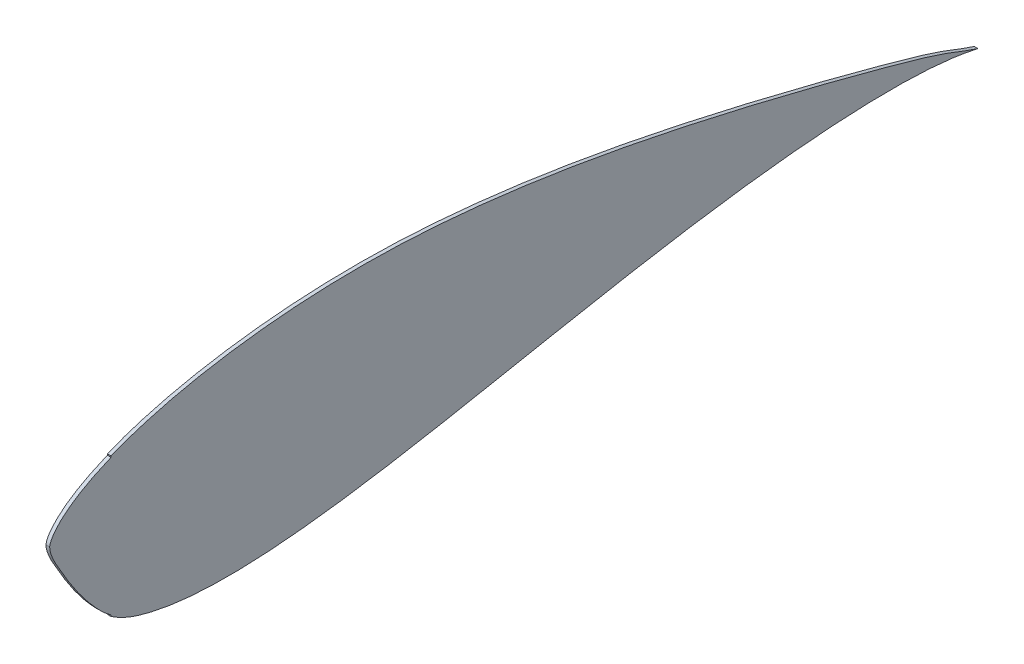
SolidWorks part; units mm, degrees
material "Custom Carbon Fiber"
ref_plane "Front Plane" through (0, 0, 0) normal (0, 0, 1) x (1, 0, 0)
ref_plane "Top Plane" through (0, 0, 0) normal (0, 1, 0) x (1, 0, 0)
ref_plane "Right Plane" through (0, 0, 0) normal (1, 0, 0) x (0, 0, -1)
ref_plane "Plane1" through (266.7, 0, 0) normal (1, 0, 0) x (0, 0, -1)
sketch "Sketch2" plane through (266.7, 0, 0) normal (1, 0, 0) x (0, 0, -1)
  line L0 (53.975, 13.9347) -> (53.975, 40.3347) construction
  line L1 (53.975, -78.4194) -> (53.975, 41.651)
  spline S0 degree 1 poles (789.2908, -24.5075) (1.0009, -0.0106) knots 0 0 1 1 construction
  spline S1 degree 1 poles (1.0009, -0.0106) (789.2908, -24.5075) knots 0 0 1 1 construction
  spline S2 degree 3 poles (789.2908, -24.5075) (785.3163, -22.9509) (777.3554, -19.854) (761.2394, -14.2813) (740.7218, -8.356) (715.9964, -1.5357) (691.2078, 5.039) (666.3726, 11.4509) (633.2067, 19.788) (591.6453, 29.7876) (541.5821, 40.9551) (491.2968, 51.0591) (440.7669, 59.8425) (389.9856, 66.9978) (347.468, 71.3203) (313.3654, 73.5459) (279.214, 74.78) (245.0298, 74.5204) (210.9104, 72.6538) (185.3864, 70.3744) (159.9555, 67.2138) (134.6626, 63.1156) (109.5715, 57.9457) (88.911, 52.5848) (72.6183, 47.5158) (60.5547, 43.2587) (48.7006, 38.47) (37.1259, 33.0527) (27.8301, 27.8819) (20.7191, 23.2421) (15.6145, 19.4551) (10.7867, 15.3221) (6.4295, 10.7521) (3.3298, 6.5207) (1.7664, 3.2894) (1.2346, 1.6296) (1.0709, 0.8085) (1.0227, 0.3736) (1.0078, 0.114) (1.0009, -0.0106) knots 0.015898 0.015898 0.015898 0.015898 0.031274 0.04665 0.077401 0.108153 0.138904 0.169656 0.200407 0.26191 0.323413 0.384916 0.446419 0.507923 0.569426 0.600177 0.630929 0.692432 0.723183 0.753935 0.784686 0.815438 0.846189 0.876941 0.892316 0.907692 0.923068 0.938444 0.95382 0.961507 0.969195 0.976883 0.984571 0.992259 0.996103 0.998025 0.998986 0.999466 0.999947 0.999947 0.999947 0.999947
  spline S3 degree 3 poles (1.0009, -0.0106) (1.0099, -0.2779) (1.0289, -0.8234) (1.1028, -1.8259) (1.4168, -3.5972) (2.4522, -7.2032) (4.5577, -12.1314) (7.6943, -17.8738) (12.0815, -25.4664) (17.7322, -34.7965) (24.9199, -45.7682) (31.4576, -54.481) (37.0476, -61.1825) (42.8536, -67.72) (50.6545, -75.2474) (61.6337, -82.3376) (73.6522, -87.3558) (86.2831, -90.8757) (99.0883, -93.5961) (116.3556, -96.1813) (138.1724, -97.7923) (164.4147, -97.9546) (190.6442, -96.7472) (216.8104, -94.5068) (242.9011, -91.4628) (277.5889, -86.5748) (320.7803, -79.293) (372.4416, -69.5597) (424.0475, -59.4829) (475.6974, -49.5822) (527.4768, -40.324) (579.4491, -32.1431) (631.6563, -25.5197) (675.3681, -21.7598) (710.4397, -20.2592) (736.775, -20.0353) (763.1229, -21.0632) (780.614, -23.101) (789.2908, -24.5075) knots 0.000052 0.000052 0.000052 0.000052 0.001013 0.001974 0.003897 0.007743 0.015433 0.023124 0.030815 0.046197 0.061579 0.07696 0.084651 0.092342 0.107724 0.123105 0.138487 0.153869 0.16925 0.184632 0.215396 0.246159 0.276922 0.307686 0.338449 0.369213 0.430739 0.492266 0.553793 0.61532 0.676847 0.738374 0.7999 0.861427 0.892191 0.922954 0.953717 0.984481 0.984481 0.984481 0.984481
  spline S4 degree 3 poles (-998.6585, -47.5543) (30.9847, 34.8549) (-3.0916, 14.059) (0.5702, -4.3968) (2.5361, -10.6164) (7.9982, -20.5501) (16.1137, -34.185) (25.7513, -48.9002) (36.932, -62.9388) (49.3364, -75.9186) (65.2269, -85.625) (84.4528, -91.7174) (106.8521, -96.1515) (132.5109, -98.5722) (161.1944, -99.0924) (192.7613, -97.7042) (227.0382, -94.5118) (263.8348, -89.6638) (302.9215, -83.3884) (344.0178, -75.9778) (386.7768, -67.7807) (430.7746, -59.2023) (475.4963, -50.6638) (520.3353, -42.6036) (564.5889, -35.4228) (607.4709, -29.4733) (648.1275, -25.0145) (685.6676, -22.1862) (719.1968, -21.0048) (747.8303, -21.2786) (770.6884, -22.8547) (787.0914, -25.0735) (843.5368, -35.1796) (888.9653, -70.6457) (1145.7828, 910.9381) knots -0.056641 -0.056641 -0.056641 -0.056641 0.001821 0.004613 0.009135 0.024676 0.044153 0.064937 0.086321 0.107138 0.1276 0.150893 0.177565 0.207668 0.241222 0.278203 0.318526 0.362031 0.408465 0.457479 0.508614 0.561296 0.614835 0.668438 0.721214 0.772202 0.820393 0.864766 0.904324 0.938132 0.965242 0.98469 0.99621 1.166448 1.166448 1.166448 1.166448 only from (0, 0) to (802.1511, -28.0117) construction
  spline S5 degree 3 poles (592.9551, -1005.8033) (880.8278, -21.537) (831.6126, -40.0251) (789.3572, -23.4586) (777.0615, -18.6436) (760.5817, -13.0401) (739.9968, -7.1233) (715.5772, -0.3798) (687.647, 7.013) (656.6835, 14.9584) (623.1589, 23.2583) (587.5492, 31.6944) (550.3192, 40.0262) (511.9148, 48.0016) (472.7617, 55.3745) (433.2622, 61.9128) (393.7959, 67.4048) (354.7199, 71.6552) (316.357, 74.5357) (278.9313, 75.7536) (242.6994, 75.3938) (207.8706, 73.5467) (174.7468, 70.259) (143.6014, 65.7682) (114.7621, 60.1875) (88.5345, 53.6285) (65.199, 46.2382) (45.0006, 38.1339) (28.1586, 29.5092) (14.871, 20.5578) (6.1442, 12.3133) (1.9481, 6.1765) (0.6391, 3.0841) (0.217, 1.668) (-1.7676, -8.4574) (19.8775, -20.5223) (-997.5581, 67.2582) knots -0.132477 -0.132477 -0.132477 -0.132477 0.003802 0.014472 0.030564 0.051299 0.077028 0.107574 0.142399 0.180921 0.222525 0.266591 0.312515 0.35971 0.407632 0.455773 0.503669 0.550901 0.597096 0.641976 0.685512 0.727353 0.767354 0.805169 0.840471 0.872937 0.902335 0.928425 0.951113 0.970253 0.985871 0.993982 0.996753 0.997907 0.999293 1.03369 1.03369 1.03369 1.03369 only from (802.1511, -28.0117) to (0, 0) construction
  spline S6 degree 3 poles (0, 0) (0.0175, -0.519) (0.0617, -1.8338) (0.5702, -4.3968) (2.5361, -10.6164) (7.9982, -20.5501) (16.1137, -34.185) (25.7513, -48.9002) (36.932, -62.9388) (49.3364, -75.9186) (65.2269, -85.625) (84.4528, -91.7174) (106.8521, -96.1515) (132.5109, -98.5722) (161.1944, -99.0924) (192.7613, -97.7042) (227.0382, -94.5118) (263.8348, -89.6638) (302.9215, -83.3884) (344.0178, -75.9778) (386.7768, -67.7807) (430.7746, -59.2023) (475.4963, -50.6638) (520.3353, -42.6036) (564.5889, -35.4228) (607.4709, -29.4733) (648.1275, -25.0145) (685.6676, -22.1862) (719.1968, -21.0048) (747.8303, -21.2786) (770.6884, -22.8547) (787.0914, -25.0735) (796.8423, -26.8193) (801.0977, -27.7751) (802.1511, -28.0117) knots 0 0 0 0 0.001821 0.004613 0.009135 0.024676 0.044153 0.064937 0.086321 0.107138 0.1276 0.150893 0.177565 0.207668 0.241222 0.278203 0.318526 0.362031 0.408465 0.457479 0.508614 0.561296 0.614835 0.668438 0.721214 0.772202 0.820393 0.864766 0.904324 0.938132 0.965242 0.98469 0.99621 1 1 1 1
  spline S7 degree 3 poles (802.1511, -28.0117) (801.1372, -27.7105) (797.2784, -26.5642) (789.3572, -23.4586) (777.0615, -18.6436) (760.5817, -13.0401) (739.9968, -7.1233) (715.5772, -0.3798) (687.647, 7.013) (656.6835, 14.9584) (623.1589, 23.2583) (587.5492, 31.6944) (550.3192, 40.0262) (511.9148, 48.0016) (472.7617, 55.3745) (433.2622, 61.9128) (393.7959, 67.4048) (354.7199, 71.6552) (316.357, 74.5357) (278.9313, 75.7536) (242.6994, 75.3938) (207.8706, 73.5467) (174.7468, 70.259) (143.6014, 65.7682) (114.7621, 60.1875) (88.5345, 53.6285) (65.199, 46.2382) (45.0006, 38.1339) (28.1586, 29.5092) (14.871, 20.5578) (6.1442, 12.3133) (1.9481, 6.1765) (0.6391, 3.0841) (0.217, 1.668) (0.0426, 0.7778) (0.0107, 0.1963) (0, 0) knots 0 0 0 0 0.003802 0.014472 0.030564 0.051299 0.077028 0.107574 0.142399 0.180921 0.222525 0.266591 0.312515 0.35971 0.407632 0.455773 0.503669 0.550901 0.597096 0.641976 0.685512 0.727353 0.767354 0.805169 0.840471 0.872937 0.902335 0.928425 0.951113 0.970253 0.985871 0.993982 0.996753 0.997907 0.999293 1 1 1 1
  dimension "D1" = 1
extrude "Boss-Extrude2" add sketch "Sketch2" against normal blind 3.175 contours L1 S3 S2 | S2 S3 L1 | S6 S7 L1 S2 S3 region at (266.7, -77.812, -54.7432) region at (266.7, -12.6463, -34.0777) region at (266.7, -6.9997, -318.0177)
